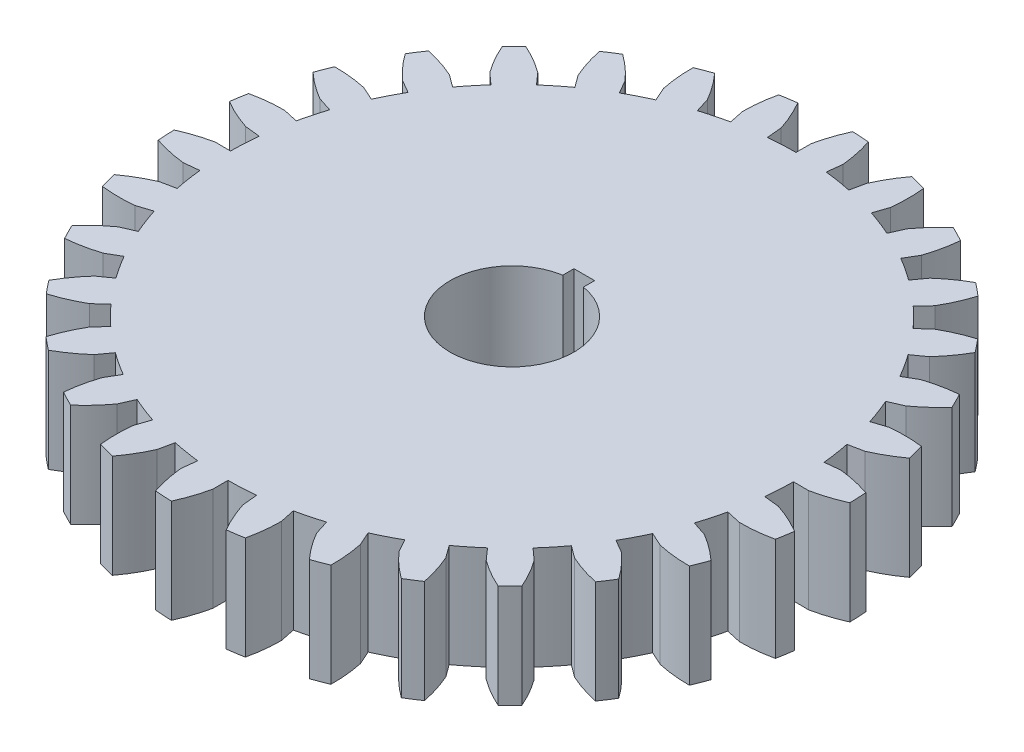
SolidWorks part; units mm, degrees
ref_plane "Front Plane" through (0, 0, 0) normal (0, 0, 1) x (1, 0, 0)
ref_plane "Top Plane" through (0, 0, 0) normal (0, 1, 0) x (1, 0, 0)
ref_plane "Right Plane" through (0, 0, 0) normal (1, 0, 0) x (0, 0, -1)
sketch "Sketch1" plane through (0, 0, 0) normal (0, 1, 0) x (1, 0, 0)
  circle A3 centre (0, 0) radius 13.75
  circle A4 centre (0, 0) radius 16
  circle A5 centre (0, 0) radius 15
  circle A6 centre (0, 0) radius 14
  circle A7 centre (0, 0) radius 14.4889
  dimension "pitch circle" = 30
  dimension "addendum circle" = 32
  dimension "root circle" = 27.5
  dimension "clearance circle" = 28
  dimension "base circle" = 28.9778
sketch "Sketch2" plane through (0, 0, 0) normal (0, 1, 0) x (1, 0, 0)
  line L0 (0, 0) -> (0, 14.4889)
  line L1 (0, 0) -> (7.2444, 12.5477) construction
  line L2 (0, 0) -> (12.5477, 7.2444) construction
  line L3 (0, 0) -> (14.4889, 0) construction
  line L4 (14.4889, 0) -> (14.4889, 22.7591) construction
  line L5 (12.5477, 7.2444) -> (4.9614, 20.3844) construction
  line L6 (7.2444, 12.5477) -> (0.6745, 16.3409) construction
  line L7 (0, 0) -> (3.1187, 14.6722)
  line L8 (0, 0) -> (1.5679, 14.9178) construction
  line L9 (0.8496, 14.9759) -> (0, 0) construction
  circle A0 centre (0, 0) radius 14.4889 construction
  circle A1 centre (0, 0) radius 15 construction
  arc A2 (1.5679, 14.9178) -> (0.1294, 14.9994) centre (0, 0) ccw
  spline S0 degree 3 poles (0, 14.4889) (1.2745, 20.4223) (9.5995, 22.7668) (14.4889, 22.7591) knots 0 0 0 0 1 1 1 1
  spline S1 degree 3 poles (1.6388, 14.3959) (1.0435, 20.4354) (-6.9629, 23.7065) (-11.8218, 24.2518) knots 0 0 0 0 1 1 1 1
  point P11 (0, 0)
  dimension "Involute Control" = 90
  dimension "Base circle quarter circumference" = 22.7591
  dimension "D1" = 15.1727
  dimension "D2" = 7.5864
  dimension "pitch circle" = 12
  dimension "Involute array" = 4
sketch "Sketch3" plane through (0, 0, 0) normal (0, 1, 0) x (1, 0, 0)
  line L0 (1.6388, 14.3959) -> (1.5552, 13.6618)
  line L1 (0, 0) -> (0, 14.4889) construction
  line L3 (0, 13.75) -> (0, 14.4889)
  arc A1 (0.502, 15.9921) -> (0, 14.4889) centre (7.0112, 12.9829) ccw
  circle A2 centre (0, 0) radius 16 construction
  circle A3 centre (0, 0) radius 13.75 construction
  arc A7 (1.6388, 14.3959) -> (1.31, 15.9463) centre (-5.4978, 13.6925) ccw
  arc A8 (1.5552, 13.6618) -> (0, 13.75) centre (0, 0) ccw
  arc A9 (1.31, 15.9463) -> (0.502, 15.9921) centre (0, 0) ccw
  circle A10 centre (0, 0) radius 14.4889 construction
  spline S0 degree 3 poles (1.6388, 14.3959) (1.0435, 20.4354) (-6.9629, 23.7065) (-11.8218, 24.2518) knots 0 0 0 0 1 1 1 1 construction
  spline S1 degree 3 poles (0, 14.4889) (1.2745, 20.4223) (9.5995, 22.7668) (14.4889, 22.7591) knots 0 0 0 0 1 1 1 1 construction
extrude "Boss-Extrude1" add sketch "Sketch3" along normal blind 5
sketch "Sketch5" plane through (0, 0, 0) normal (1, 0, 0) x (0, 0, -1)
  line L0 (0, 0) -> (0, 5.4709) construction
pattern_circular "CirPattern4" count 30 over 360 about axis through (0, 0, 0) along (0, 1, 0) reverse direction yes of bodies 101
sketch "Sketch6" plane through (0, 0, 0) normal (0, 1, 0) x (1, 0, 0)
  circle A0 centre (0, 0) radius 13.75 construction
  circle A1 centre (0, 0) radius 13.75
extrude "Boss-Extrude2" add sketch "Sketch6" along normal up to surface (5 mm away) up to face at (2.2427, 5, 14.5662)
sketch "Sketch7" plane through (0, 5, 0) normal (0, 1, 0) x (1, 0, 0)
  line L1 (-0.5, 3.5) -> (0.5, 3.5)
  line L2 (-0.5, 3.5) -> (-0.5, 2.5)
  line L3 (-0.5, 2.5) -> (0.5, 2.5)
  line L4 (0.5, 3.5) -> (0.5, 2.5)
  line L5 (-0.5, 3.5) -> (0.5, 2.5) construction
  line L6 (-0.5, 2.5) -> (0.5, 3.5) construction
  circle A0 centre (0, 0) radius 3
  point P3 (0, 3)
  dimension "D1" = 6
  dimension "D2" = 1
extrude "Cut-Extrude1" cut sketch "Sketch7" against normal through all contours L2 A0 L4 L3 | L4 A0 L2 L3 | L4 L3 L2 L1 region at (0, 5, -2.7432) region at (0, 5, 0.048)
equation "\"Module\"= 1"
equation "\"Teeth number\" = 30"
equation "\"Pressure angle\"= 15"
equation "\"pitch circle@Sketch1\"= \"Module\" * \"Teeth number\""
equation "\"addendum circle@Sketch1\"= \"pitch circle@Sketch1\" + ( \"Module\" * 2 )"
equation "\"root circle@Sketch1\"= \"pitch circle@Sketch1\" - ( ( \"Module\" * 1.25 ) * 2 )"
equation "\"clearance circle@Sketch1\"= \"pitch circle@Sketch1\" - ( \"Module\" * 2 )"
equation "\"base circle@Sketch1\"= \"pitch circle@Sketch1\" * cos ( \"Pressure angle\" )"
equation "\"D1@Sketch2\"=\"Base circle quarter circumference@Sketch2\"/3*2"
equation "\"D2@Sketch2\"=\"Base circle quarter circumference@Sketch2\"/3"
equation "\"pitch circle@Sketch2\"=360/\"Teeth number\""
equation "\"D1@CirPattern4\"=\"Teeth number\""
equation "\"Base circle quarter circumference@Sketch2\"= \"base circle@Sketch1\" * pi / 4"
